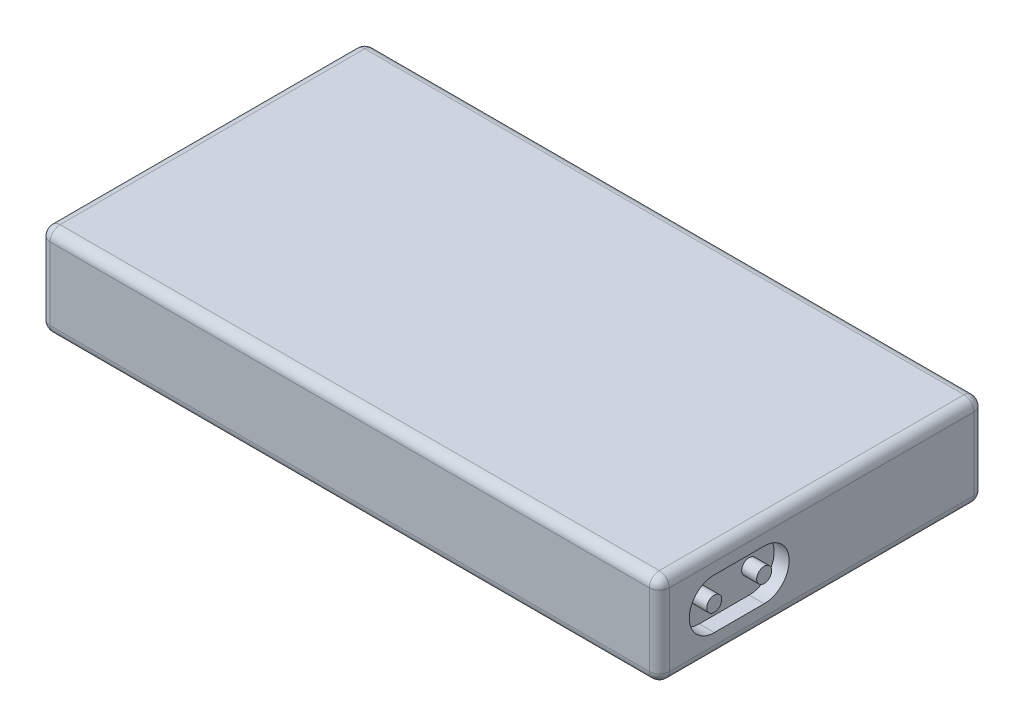
SolidWorks part; units mm, degrees
material "Резина"
ref_plane "Спереди" through (0, 0, 0) normal (0, 0, 1) x (1, 0, 0)
ref_plane "Сверху" through (0, 0, 0) normal (0, 1, 0) x (1, 0, 0)
ref_plane "Справа" through (0, 0, 0) normal (1, 0, 0) x (0, 0, -1)
sketch "Эскиз1" plane through (0, 0, 0) normal (0, 1, 0) x (1, 0, 0)
  line L0 (0, 0) -> (124, 0)
  line L1 (0, 0) -> (0, 65)
  line L2 (124, 0) -> (124, 65)
  line L3 (0, 65) -> (124, 65)
  dimension "D1" = 124
  dimension "D2" = 65
extrude "Бобышка-Вытянуть1" add sketch "Эскиз1" along normal blind 18.5
sketch "Эскиз2" plane through (124, 0, 0) normal (1, 0, 0) x (0, 0, -1)
  line L0 (0, 9.25) -> (65, 9.25) construction
  line L1 (0, 18.5) -> (0, 0) construction
  line L2 (65, 18.5) -> (65, 0) construction
  line L3 (5, 15.25) -> (5, 3.25) construction
  line L4 (5, 15.25) -> (27, 15.25) construction
  line L5 (5, 3.25) -> (27, 3.25) construction
  line L6 (27, 15.25) -> (27, 3.25) construction
  line L7 (11, 9.25) -> (21, 9.25) construction
  line L8 (11, 14.25) -> (21, 14.25)
  line L9 (11, 4.25) -> (21, 4.25)
  line L10 (16, 15.25) -> (16, 3.25) construction
  arc A0 (11, 14.25) -> (11, 4.25) centre (11, 9.25) ccw
  arc A1 (21, 4.25) -> (21, 14.25) centre (21, 9.25) ccw
  circle A2 centre (11, 9.25) radius 1.5
  circle A3 centre (21, 9.25) radius 1.5
  point P6 (27, 9.25)
  point P11 (16, 9.25)
  dimension "D5" = 5
  dimension "D6" = 3
  dimension "D1" = 5
  dimension "D2" = 22
  dimension "D3" = 12
  dimension "D4" = 10
extrude "Вырез-Вытянуть1" cut sketch "Эскиз2" against normal blind 3
sketch "Эскиз3" plane through (0, 0, 0) normal (-1, 0, 0) x (0, 0, 1)
  line L0 (-65, 9.25) -> (0, 9.25) construction
  line L1 (-65, 18.5) -> (-65, 0) construction
  line L2 (0, 18.5) -> (0, 0) construction
  line L3 (-59, 12.75) -> (-59, 5.75)
  line L4 (-59, 12.75) -> (-45, 12.75)
  line L5 (-59, 5.75) -> (-45, 5.75)
  line L6 (-45, 12.75) -> (-45, 5.75)
  line L7 (-58, 8.75) -> (-58, 6.75)
  line L8 (-58, 8.75) -> (-46, 8.75)
  line L9 (-58, 6.75) -> (-46, 6.75)
  line L10 (-46, 8.75) -> (-46, 6.75)
  point P6 (-59, 9.25)
  dimension "D1" = 14
  dimension "D2" = 6
  dimension "D3" = 7
  dimension "D4" = 2
  dimension "D5" = 1
  dimension "D6" = 1
  dimension "D7" = 1
extrude "Вырез-Вытянуть2" cut sketch "Эскиз3" against normal blind 3
sketch "Эскиз4" plane through (0, 0, 0) normal (-1, 0, 0) x (0, 0, 1)
  line L0 (-65, 9.25) -> (0, 9.25) construction
  line L1 (-65, 18.5) -> (-65, 0) construction
  line L2 (0, 18.5) -> (0, 0) construction
  line L3 (-20, 12.75) -> (-20, 5.75) construction
  line L4 (-20, 12.75) -> (-6, 12.75) construction
  line L5 (-20, 5.75) -> (-6, 5.75) construction
  line L6 (-6, 12.75) -> (-6, 5.75) construction
  line L7 (-19, 9.25) -> (-16, 12.25)
  line L8 (-16, 12.25) -> (-10, 12.25)
  line L9 (-10, 12.25) -> (-7, 9.25)
  line L10 (-10, 6.25) -> (-7, 9.25)
  line L11 (-16, 6.25) -> (-10, 6.25)
  line L12 (-19, 9.25) -> (-16, 6.25)
  line L13 (-13, 12.25) -> (-13, 6.25) construction
  line L14 (-16, 12.25) -> (-16, 6.25) construction
  line L15 (-10, 12.25) -> (-10, 6.25) construction
  line L16 (-14, 9.25) -> (-12, 9.25) construction
  line L17 (-13, 12.75) -> (-13, 5.75) construction
  circle A0 centre (-16, 9.25) radius 0.5
  circle A1 centre (-14, 9.25) radius 0.5
  circle A2 centre (-12, 9.25) radius 0.5
  circle A3 centre (-10, 9.25) radius 0.5
  point P6 (-20, 9.25)
  point P27 (-13, 9.25)
  dimension "D8" = 2
  dimension "D9" = 2
  dimension "D10" = 2
  dimension "D11" = 1
  dimension "D1" = 14
  dimension "D2" = 6
  dimension "D3" = 7
  dimension "D4" = 45
  dimension "D6" = 6
  dimension "D7" = 6
extrude "Вырез-Вытянуть3" cut sketch "Эскиз4" against normal blind 3
fillet "Скругление1" radius 2 4 edges at (124, 18.5, -32.5) (62, 18.5, -65) (0, 18.5, -32.5) (62, 18.5, 0)
fillet "Скругление2" radius 2 4 edges at (62, 0, 0) (124, 0, -32.5) (62, 0, -65) (0, 0, -32.5)
fillet "Скругление3" radius 2 6 edges at (123.4142, 17.9142, -0.5858) (123.4142, 0.5858, -0.5858) (0.5858, 17.9142, -0.5858) (0.5858, 0.5858, -0.5858) (124, 9.25, 0) (0, 9.25, 0)
fillet "Скругление4" radius 2 6 edges at (0.5858, 17.9142, -64.4142) (0.5858, 0.5858, -64.4142) (123.4142, 17.9142, -64.4142) (123.4142, 0.5858, -64.4142) (0, 9.25, -65) (124, 9.25, -65)
